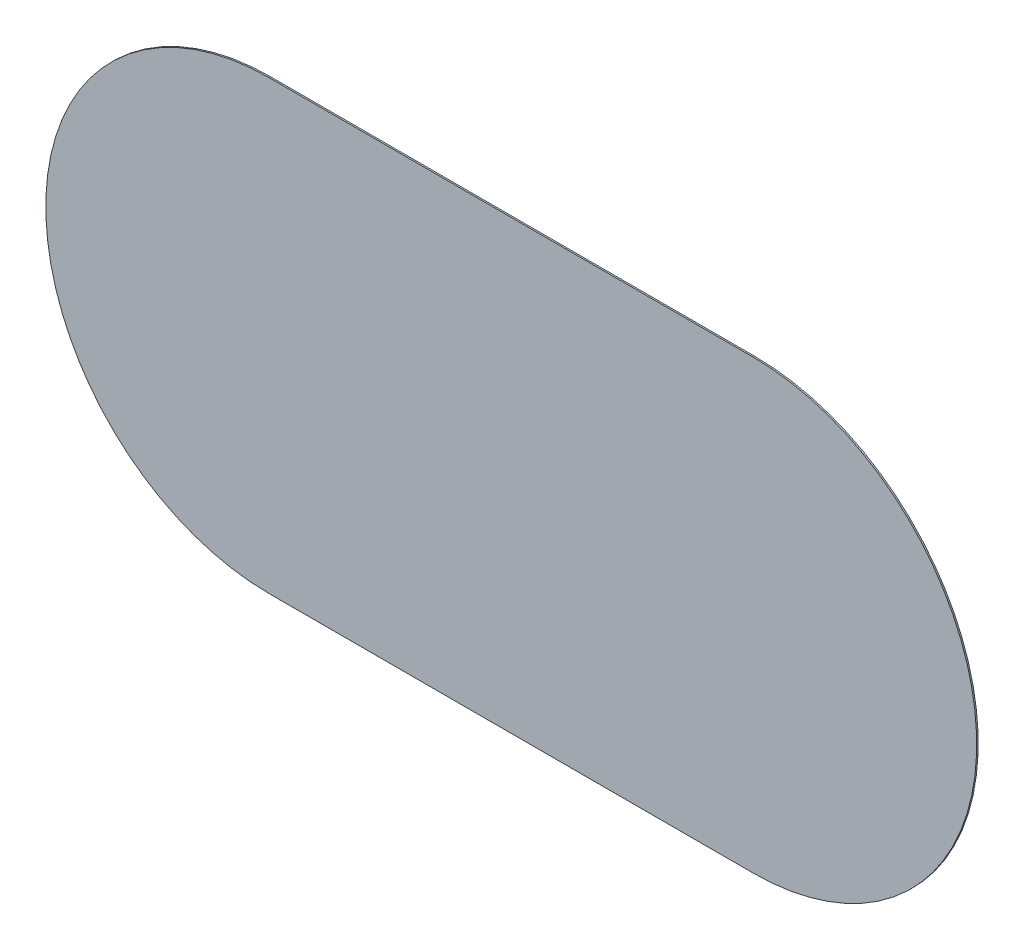
SolidWorks part; units mm, degrees
material "Plain Carbon Steel"
ref_plane "Front Plane" through (0, 0, 0) normal (0, 0, 1) x (1, 0, 0)
ref_plane "Top Plane" through (0, 0, 0) normal (0, 1, 0) x (1, 0, 0)
ref_plane "Right Plane" through (0, 0, 0) normal (1, 0, 0) x (0, 0, -1)
sketch "Sketch1" plane through (0, 0, 0) normal (0, 0, 1) x (1, 0, 0)
  line L0 (-162.5, 0) -> (162.5, 0) construction
  line L1 (-162.5, 150) -> (162.5, 150)
  line L2 (-162.5, -150) -> (162.5, -150)
  arc A0 (-162.5, 150) -> (-162.5, -150) centre (-162.5, 0) ccw
  arc A1 (162.5, -150) -> (162.5, 150) centre (162.5, 0) ccw
  point P3 (0, 0)
  dimension "D2" = 150
  dimension "D1" = 325
base flange "Base-Flange1" sketch "Sketch1" thickness 1 reverse thickness direction no parameters "D1"=0.7366
sketch "Bend-Lines1" [suppressed] plane through (0, 0, 0) normal (0, 1, 0) x (1, 0, 0)
sketch "Bounding-Box1" [suppressed] plane through (0, 0, 0) normal (0, 1, 0) x (1, 0, 0)
sheet metal parameters "Sheet-Metal1" thickness 1 parameters "D1"=0.7366
flat pattern "Flat-Pattern1" [suppressed]
sketch "Bend-Lines2" plane through (0, 0, 0) normal (0, 1, 0) x (1, 0, 0)
sketch3d "Bounding-Box2" [suppressed]
  line L0 (-180, -180, 0) -> (505, -180, 0) construction
  line L1 (-180, 180, 0) -> (505, 180, 0) construction
  line L2 (-180, -180, 0) -> (-180, 180, 0) construction
  line L3 (505, -180, 0) -> (505, 180, 0) construction
